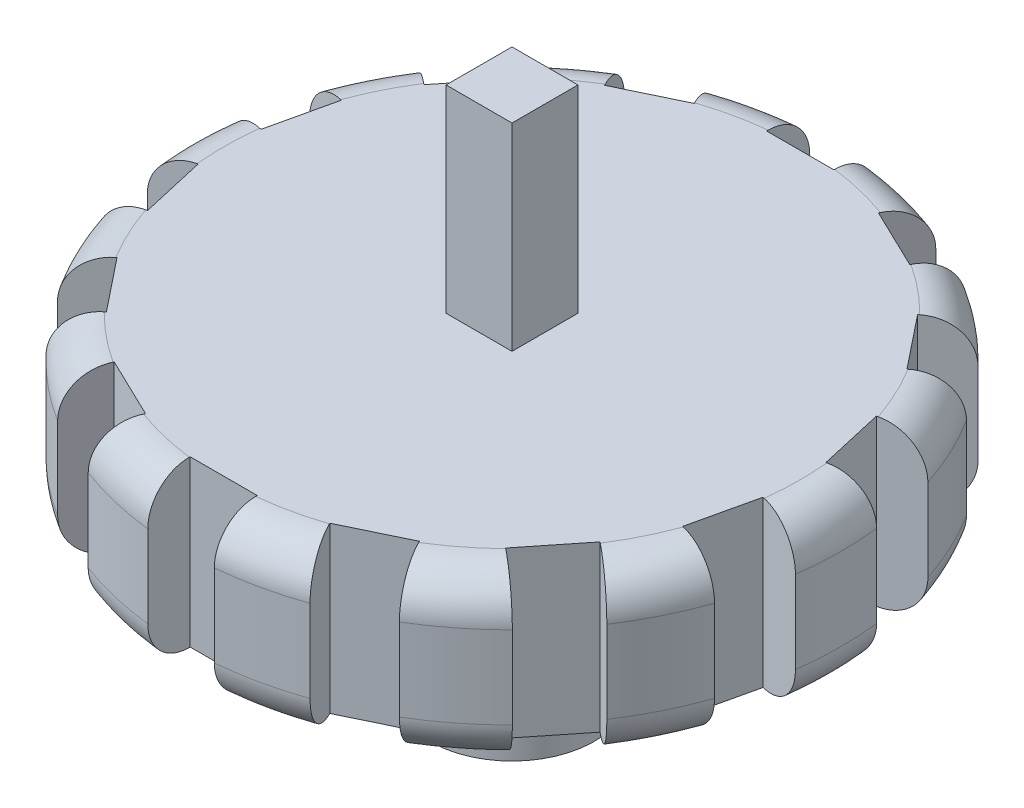
SolidWorks part; units mm, degrees
ref_plane "前视基准面" through (0, 0, 0) normal (0, 0, 1) x (1, 0, 0)
ref_plane "上视基准面" through (0, 0, 0) normal (0, 1, 0) x (1, 0, 0)
ref_plane "右视基准面" through (0, 0, 0) normal (1, 0, 0) x (0, 0, -1)
sketch "草图1" plane through (0, 0, 0) normal (0, 1, 0) x (1, 0, 0)
  circle A0 centre (-15.2372, 0.4) radius 4
extrude "凸台-拉伸1" add sketch "草图1" along normal blind 2 contours A0
sketch "草图2" plane through (0, 2, 0) normal (0, 1, 0) x (1, 0, 0)
  line L1 (-15.6372, 0.8) -> (-14.8372, 0.8)
  line L2 (-15.6372, 0.8) -> (-15.6372, 0)
  line L3 (-15.6372, 0) -> (-14.8372, 0)
  line L4 (-14.8372, 0.8) -> (-14.8372, 0)
  line L5 (-15.6372, 0.8) -> (-14.8372, 0) construction
  line L6 (-15.6372, 0) -> (-14.8372, 0.8) construction
  point P0 (-15.2372, 0.4)
extrude "凸台-拉伸2" add sketch "草图2" along normal blind 2.4
sketch "草图3" plane through (0, 0, 0) normal (0, -1, 0) x (1, 0, 0)
  circle A0 centre (-15.2372, -0.4) radius 1
extrude "凸台-拉伸3" add sketch "草图3" along normal blind 2
fillet "圆角2" radius 0.5 2 edges at (-15.2372, 0, 3.6) (-15.2372, 2, 3.6)
sketch "草图6" plane through (0, 2, 0) normal (0, 1, 0) x (1, 0, 0)
  line L0 (-16.7431, -3.5795) -> (-16.4057, -2.879)
  line L1 (-14.8673, -3.8388) -> (-15.6824, -3.8388)
  line L2 (-14.8673, -3.8388) -> (-14.8673, -3.0612)
  line L3 (-14.8673, -3.0612) -> (-15.6824, -3.0612)
  line L4 (-15.6824, -3.8388) -> (-15.6824, -3.0612)
  line L5 (-16.7431, -3.5795) -> (-17.4775, -3.2258)
  line L6 (-17.4775, -3.2258) -> (-17.1401, -2.5253)
  line L7 (-16.4057, -2.879) -> (-17.1401, -2.5253)
  line L8 (-18.3206, -2.5321) -> (-17.7127, -2.0473)
  line L9 (-18.3206, -2.5321) -> (-18.8288, -1.8948)
  line L10 (-18.8288, -1.8948) -> (-18.2209, -1.41)
  line L11 (-17.7127, -2.0473) -> (-18.2209, -1.41)
  line L12 (-19.2874, -0.9039) -> (-18.5294, -0.7309)
  line L13 (-19.2874, -0.9039) -> (-19.4688, -0.1092)
  line L14 (-19.4688, -0.1092) -> (-18.7108, 0.0638)
  line L15 (-18.5294, -0.7309) -> (-18.7108, 0.0638)
  line L16 (-19.4521, 0.9825) -> (-18.694, 0.8095)
  line L17 (-19.4521, 0.9825) -> (-19.2707, 1.7772)
  line L18 (-19.2707, 1.7772) -> (-18.5126, 1.6042)
  line L19 (-18.694, 0.8095) -> (-18.5126, 1.6042)
  line L20 (-18.7819, 2.7536) -> (-18.174, 2.2688)
  line L21 (-18.7819, 2.7536) -> (-18.2737, 3.3909)
  line L22 (-18.2737, 3.3909) -> (-17.6658, 2.9061)
  line L23 (-18.174, 2.2688) -> (-17.6658, 2.9061)
  line L24 (-17.4097, 4.0585) -> (-17.0723, 3.3579)
  line L25 (-17.4097, 4.0585) -> (-16.6753, 4.4122)
  line L26 (-16.6753, 4.4122) -> (-16.3379, 3.7116)
  line L27 (-17.0723, 3.3579) -> (-16.3379, 3.7116)
  line L28 (-15.6072, 4.6388) -> (-15.6072, 3.8612)
  line L29 (-15.6072, 4.6388) -> (-14.7921, 4.6388)
  line L30 (-14.7921, 4.6388) -> (-14.7921, 3.8612)
  line L31 (-15.6072, 3.8612) -> (-14.7921, 3.8612)
  line L32 (-13.7314, 4.3795) -> (-14.0688, 3.679)
  line L33 (-13.7314, 4.3795) -> (-12.997, 4.0258)
  line L34 (-12.997, 4.0258) -> (-13.3344, 3.3253)
  line L35 (-14.0688, 3.679) -> (-13.3344, 3.3253)
  line L36 (-12.1539, 3.3321) -> (-12.7618, 2.8473)
  line L37 (-12.1539, 3.3321) -> (-11.6457, 2.6948)
  line L38 (-11.6457, 2.6948) -> (-12.2536, 2.21)
  line L39 (-12.7618, 2.8473) -> (-12.2536, 2.21)
  line L40 (-11.1871, 1.7039) -> (-11.9451, 1.5309)
  line L41 (-11.1871, 1.7039) -> (-11.0057, 0.9092)
  line L42 (-11.0057, 0.9092) -> (-11.7637, 0.7362)
  line L43 (-11.9451, 1.5309) -> (-11.7637, 0.7362)
  line L44 (-11.0224, -0.1825) -> (-11.7805, -0.0095)
  line L45 (-11.0224, -0.1825) -> (-11.2038, -0.9772)
  line L46 (-11.2038, -0.9772) -> (-11.9619, -0.8042)
  line L47 (-11.7805, -0.0095) -> (-11.9619, -0.8042)
  line L48 (-11.6926, -1.9536) -> (-12.3005, -1.4688)
  line L49 (-11.6926, -1.9536) -> (-12.2008, -2.5909)
  line L50 (-12.2008, -2.5909) -> (-12.8087, -2.1061)
  line L51 (-12.3005, -1.4688) -> (-12.8087, -2.1061)
  line L52 (-13.0648, -3.2585) -> (-13.4022, -2.5579)
  line L53 (-13.0648, -3.2585) -> (-13.7992, -3.6122)
  line L54 (-13.7992, -3.6122) -> (-14.1366, -2.9116)
  line L55 (-13.4022, -2.5579) -> (-14.1366, -2.9116)
  point P59 (-15.2372, 0.4)
  dimension "D1" = 14
extrude "切除-拉伸4" cut sketch "草图6" against normal blind 2
